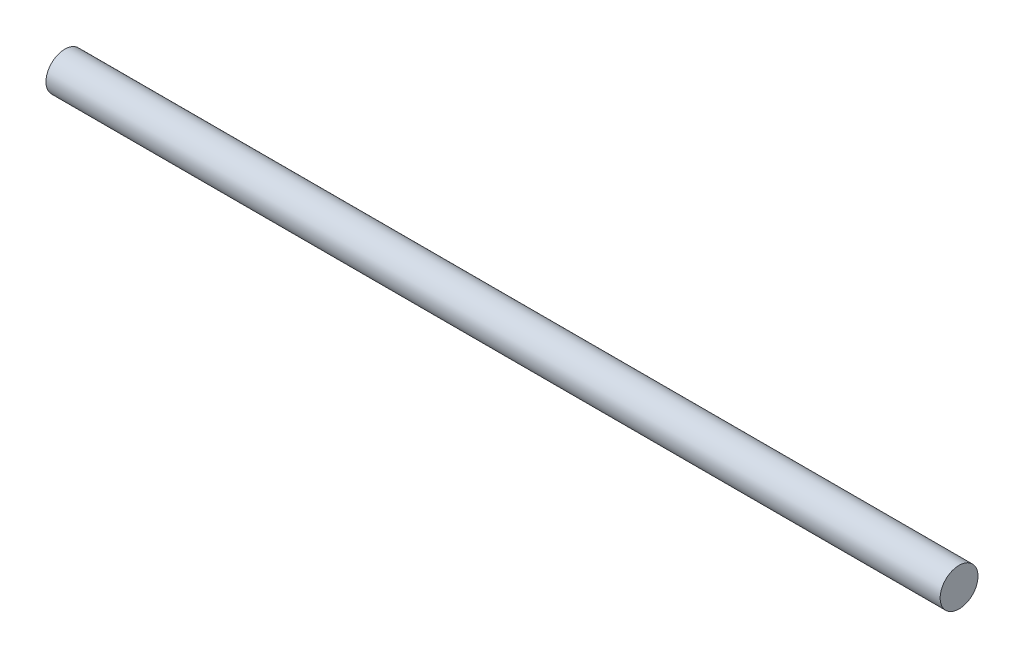
SolidWorks part; units mm, degrees
ref_plane "Front Plane" through (0, 0, 0) normal (0, 0, 1) x (1, 0, 0)
ref_plane "Top Plane" through (0, 0, 0) normal (0, 1, 0) x (1, 0, 0)
ref_plane "Right Plane" through (0, 0, 0) normal (1, 0, 0) x (0, 0, -1)
sketch "Sketch1" plane through (0, 0, 0) normal (1, 0, 0) x (0, 0, -1)
  circle A0 centre (0, 0) radius 3.175
  dimension "D1" = 6.35
extrude "Boss-Extrude1" add sketch "Sketch1" along normal mid plane 150
